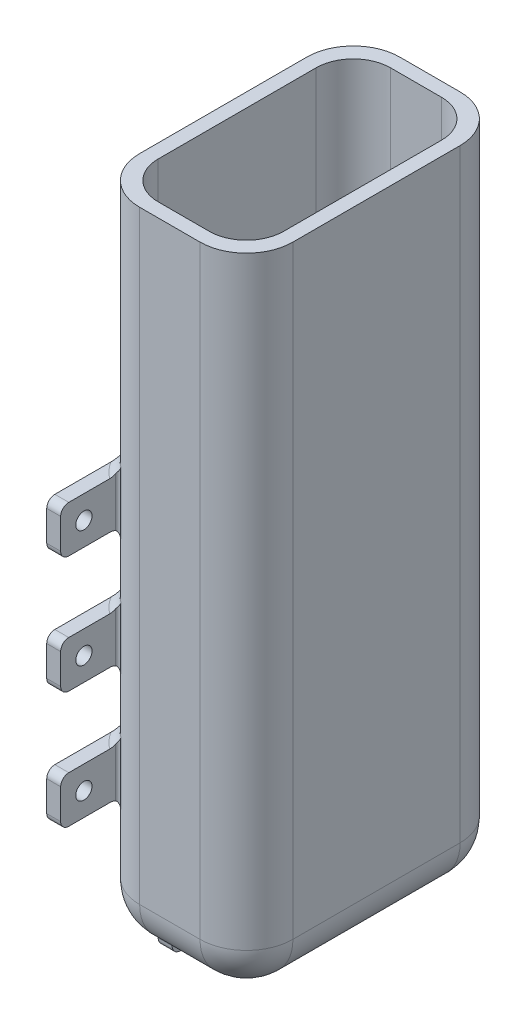
SolidWorks part; units mm, degrees
ref_plane "Plan de face" through (0, 0, 0) normal (0, 0, 1) x (1, 0, 0)
ref_plane "Plan de dessus" through (0, 0, 0) normal (0, 1, 0) x (1, 0, 0)
ref_plane "Plan de droite" through (0, 0, 0) normal (1, 0, 0) x (0, 0, -1)
sketch "Esquisse1" plane through (0, 0, 0) normal (0, 1, 0) x (1, 0, 0)
  line L3 (16.5, 28) -> (-16.5, 28)
  line L4 (13.5, -25) -> (-13.5, -25)
  line L5 (13.5, -25) -> (13.5, 25)
  line L6 (13.5, 25) -> (-13.5, 25)
  line L7 (-13.5, -25) -> (-13.5, 25)
  line L8 (13.5, -25) -> (-13.5, 25) construction
  line L9 (13.5, 25) -> (-13.5, -25) construction
  line L10 (-16.5, -28) -> (-16.5, 28)
  line L11 (16.5, -28) -> (-16.5, -28)
  line L12 (16.5, -28) -> (16.5, 28)
  point P10 (0, 0)
  dimension "D3" = 27
  dimension "D4" = 50
  dimension "D5" = 3
extrude "Boss.-Extru.1" add sketch "Esquisse1" along normal blind 137 contours L3 | L11 L12 L3 L10 L4 L7 L6 L5 region at (15.85, 0, 0)
extrude "Boss.-Extru.2" add sketch "Esquisse1<3>" against normal blind 3 contours L7 L4 L5 L6 | L11 L12 L3 L10 L4 L7 L6 L5 region at (15.85, 0, 0) region at (0, 0, 0)
sketch "Esquisse1<3>" plane through (0, 0, 0) normal (0, 1, 0) x (1, 0, 0) same geometry as "Esquisse1"
fillet "Congé1" radius 10 8 edges at (0, -3, -28) (-16.5, -3, 0) (0, -3, 28) (16.5, -3, 0) (16.5, 67, 28) (-16.5, 67, 28) (-16.5, 67, -28) (16.5, 67, -28)
sketch "Esquisse2" plane through (-16.5, 0, 0) normal (-1, 0, 0) x (0, 0, 1)
  line L0 (-28, 7) -> (-28, 137) construction
  line L1 (-18, -3) -> (-38, -3) construction
  line L2 (-18, -3) -> (-18, 7) construction
  line L3 (-18, 7) -> (-38, 7) construction
  line L4 (-38, -3) -> (-38, 7) construction
  line L5 (0, 0) -> (0, -3) construction
  line L6 (-18, 22.2) -> (-38, 22.2)
  line L7 (38, -3) -> (38, 7) construction
  line L8 (18, 7) -> (38, 7) construction
  line L9 (18, -3) -> (18, 7) construction
  line L10 (18, -3) -> (38, -3) construction
  line L11 (18, -3) -> (-18, -3) construction
  line L12 (-18, 22.2) -> (-18, 32.2)
  line L13 (-18, 32.2) -> (-38, 32.2)
  line L14 (-38, 22.2) -> (-38, 32.2)
  line L15 (-18, 47.4) -> (-38, 47.4)
  line L16 (-18, 47.4) -> (-18, 57.4)
  line L17 (-18, 57.4) -> (-38, 57.4)
  line L18 (-38, 47.4) -> (-38, 57.4)
  line L19 (-18, 72.6) -> (-38, 72.6)
  line L20 (-18, 72.6) -> (-18, 82.6)
  line L21 (-18, 82.6) -> (-38, 82.6)
  line L22 (-38, 72.6) -> (-38, 82.6)
  line L23 (38, 72.6) -> (38, 82.6)
  line L24 (18, 82.6) -> (38, 82.6)
  line L25 (18, 72.6) -> (18, 82.6)
  line L26 (18, 72.6) -> (38, 72.6)
  line L27 (38, 47.4) -> (38, 57.4)
  line L28 (18, 57.4) -> (38, 57.4)
  line L29 (18, 47.4) -> (18, 57.4)
  line L30 (18, 47.4) -> (38, 47.4)
  line L31 (38, 22.2) -> (38, 32.2)
  line L32 (18, 32.2) -> (38, 32.2)
  line L33 (18, 22.2) -> (18, 32.2)
  line L34 (18, 22.2) -> (38, 22.2)
  line L35 (-14, -3) -> (-18, -3) construction
  line L36 (-14, -3) -> (-4, -3) construction
  line L37 (-14, -3) -> (-14, -13)
  line L38 (-14, -13) -> (-4, -13)
  line L39 (-4, -3) -> (-4, -13)
  line L44 (-4, -3) -> (0, -3) construction
  line L45 (14, -3) -> (4, -3) construction
  line L46 (14, -3) -> (14, -13)
  line L47 (14, -13) -> (4, -13)
  line L48 (4, -3) -> (4, -13)
  line L49 (-14, -3) -> (-14, 7)
  line L50 (-18, 7) -> (18, 7) construction
  line L51 (-14, 7) -> (-4, 7)
  line L52 (-4, 7) -> (-4, -3)
  line L53 (4, -3) -> (4, 7)
  line L54 (4, 7) -> (14, 7)
  line L55 (14, 7) -> (14, -3)
  line L56 (-28, 7) -> (-28, 2) construction
  line L57 (-28, 2) -> (-38, 2) construction
  circle A0 centre (-33, 2) radius 1.75 construction
  circle A1 centre (33, 2) radius 1.75 construction
  circle A2 centre (-33, 27.2) radius 1.75
  circle A3 centre (-33, 52.4) radius 1.75
  circle A4 centre (-33, 77.6) radius 1.75
  circle A5 centre (33, 77.6) radius 1.75
  circle A6 centre (33, 52.4) radius 1.75
  circle A7 centre (33, 27.2) radius 1.75
  circle A8 centre (-9, -8) radius 1.75
  circle A9 centre (9, -8) radius 1.75
  point P10 (-38, 2)
  point P71 (4, -8)
  point P72 (9, -13)
  point P73 (-9, -13)
  point P80 (-34.2464, 2)
  dimension "D3" = 3.5
  dimension "D6" = 20
  dimension "D1" = 10
  dimension "D2" = 10
  dimension "D4" = 4
  dimension "D5" = 25.2
  dimension "D7" = 10
extrude "Boss.-Extru.4" add sketch "Esquisse2" against normal blind 3
fillet "Congé2" radius 1.75 32 edges at (-15, 22.2, 38) (-15, 32.2, 38) (-15, 47.4, 38) (-15, 57.4, 38) (-15, 72.6, 38) (-15, 82.6, 38) (-15, 82.6, -38) (-15, 72.6, -38) (-15, 57.4, -38) (-15, 47.4, -38) (-15, 32.2, -38) (-15, 22.2, -38) (-15, -13, 14) (-15, -13, 4) (-15, -13, -4) (-15, -13, -14) (-15.7195, 32.2, -21.873) (-15.7195, 57.4, -21.873) (-15.7195, 82.6, -21.873) (-15.7195, 72.6, -21.873) (-15.7195, 47.4, -21.873) (-15.7195, 22.2, -21.873) (-15.7195, 47.4, 21.873) (-15.7195, 72.6, 21.873) (-15.7195, 82.6, 21.873) (-15.7195, 57.4, 21.873) (-15.7195, 32.2, 21.873) (-15.7195, 22.2, 21.873) (-15.7195, 3.127, -4) (-15.7195, 3.127, -14) (-15.7195, 3.127, 4) (-15.7195, 3.127, 14)
fillet "Congé3" radius 0.5 8 edges at (-13.5, 27.2, -25.1414) (-13.5, 77.6, -25.1414) (-13.5, 52.4, -25.1414) (-13.5, 27.2, 25.1414) (-13.5, 52.4, 25.1414) (-13.5, 77.6, 25.1414) (-13.5, -0.1414, 9) (-13.5, -0.1414, -9)
fillet "Congé4" radius 8 8 edges at (-13.5, 0, 0) (0, 0, -25) (13.5, 0, 0) (0, 0, 25) (-13.5, 68.5, -25) (13.5, 68.5, -25) (13.5, 68.5, 25) (-13.5, 68.5, 25)
